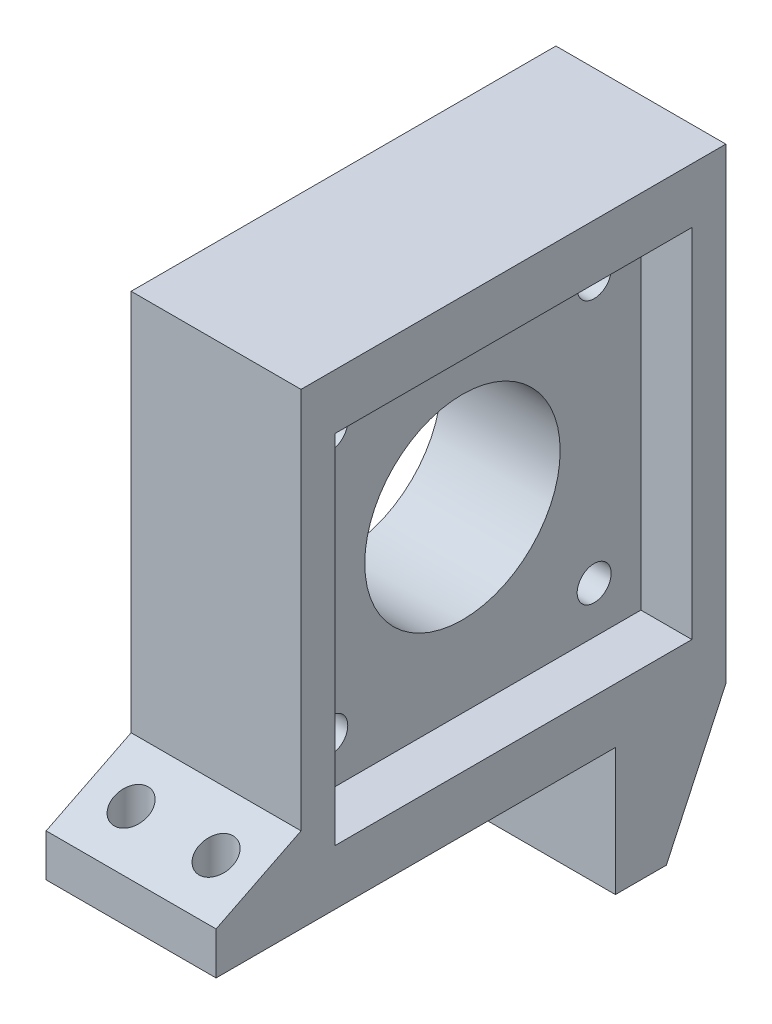
SolidWorks part; units mm, degrees
ref_plane "Front Plane" through (0, 0, 0) normal (0, 0, 1) x (1, 0, 0)
ref_plane "Top Plane" through (0, 0, 0) normal (0, 1, 0) x (1, 0, 0)
ref_plane "Right Plane" through (0, 0, 0) normal (1, 0, 0) x (0, 0, -1)
sketch "Sketch1" plane through (0, 0, 0) normal (0, 1, 0) x (1, 0, 0)
  line L1 (0, 0) -> (-20, 0)
  line L2 (0, 0) -> (0, -50)
  line L3 (0, -50) -> (-20, -50)
  line L4 (-20, 0) -> (-20, -50)
  dimension "D1" = 20
  dimension "D2" = 50
extrude "Boss-Extrude1" add sketch "Sketch1" along normal blind 70
sketch "Sketch2" plane through (0, 0, 0) normal (1, 0, 0) x (0, 0, -1)
  line L0 (-50, 70) -> (0, 70) construction
  line L1 (0, 70) -> (0, 0) construction
  line L2 (0, 42.5) -> (-50, 42.5) construction
  line L3 (-25, 70) -> (-25, 0) construction
  line L4 (-25, 70) -> (-25, 0) construction
  line L7 (-50, 70) -> (-50, 0) construction
  circle A0 centre (-9.5, 58) radius 2
  circle A4 centre (-25, 42.5) radius 11.5
  circle A5 centre (-9.5, 27) radius 2
  circle A8 centre (-40.5, 27) radius 2
  circle A9 centre (-40.5, 58) radius 2
  dimension "D1" = 4
  dimension "D2" = 12
  dimension "D3" = 15.5
  dimension "D6" = 23
  dimension "D7" = 0
  dimension "D8" = 0
  dimension "D4" = 15.5
  dimension "D5" = 0
extrude "Cut-Extrude2" cut sketch "Sketch2" against normal blind 60
sketch "Sketch4" plane through (0, 0, 0) normal (1, 0, 0) x (0, 0, -1)
  line L1 (-50, 0) -> (-13, 0)
  line L2 (-50, 0) -> (-50, 15)
  line L3 (-50, 15) -> (-13, 15)
  line L4 (-13, 0) -> (-13, 15)
  circle A0 centre (-25, 42.5) radius 11.5 construction
  dimension "D1" = 15
  dimension "D2" = 12
extrude "Cut-Extrude3" cut sketch "Sketch4" against normal blind 60
sketch "Sketch8" plane through (0, 0, 0) normal (0, 0, -1) x (-1, 0, 0)
  line L0 (0, 0) -> (20, 0) construction
  line L1 (20, 70) -> (20, 0) construction
  circle A0 centre (15, 6) radius 2
  dimension "D1" = 4
  dimension "D2" = 6
  dimension "D3" = 5
extrude "Cut-Extrude5" cut sketch "Sketch8" against normal blind 15
sketch "Sketch9" plane through (0, 0, 0) normal (1, 0, 0) x (0, 0, -1)
  line L0 (0, 42.5) -> (-50, 42.5) construction
  line L1 (-4, 63.5) -> (-46, 63.5)
  line L2 (-4, 63.5) -> (-4, 21.5)
  line L3 (-4, 21.5) -> (-46, 21.5)
  line L4 (-46, 63.5) -> (-46, 21.5)
  line L5 (0, 70) -> (0, 0) construction
  line L6 (-50, 70) -> (-50, 15) construction
  line L7 (-25, 70) -> (-25, 15) construction
  line L8 (-50, 70) -> (0, 70) construction
  line L9 (-13, 15) -> (-50, 15) construction
  circle A0 centre (-25, 42.5) radius 11.5 construction
  dimension "D1" = 0
  dimension "D2" = 42
  dimension "D3" = 21
  dimension "D4" = 42
  dimension "D5" = 21
  dimension "D6" = 0
extrude "Cut-Extrude6" cut sketch "Sketch9" against normal blind 6
sketch "Sketch10" plane through (0, 0, 0) normal (0, 0, -1) x (-1, 0, 0)
  line L0 (0, 70) -> (0, 0) construction
  circle A0 centre (5, 6) radius 2
  circle A1 centre (15, 6) radius 2 construction
  dimension "D1" = 4
  dimension "D2" = 5
  dimension "D3" = 0
extrude "Cut-Extrude7" cut sketch "Sketch10" against normal blind 7
sketch "Sketch11" plane through (0, 0, 0) normal (1, 0, 0) x (0, 0, -1)
  line L7 (-7, 0) -> (0, 0)
  line L8 (-13, 0) -> (0, 0) construction
  line L9 (0, 0) -> (0, 15)
  line L10 (0, 70) -> (0, 0) construction
  line L11 (0, 15) -> (-7, 0)
  line L12 (-13, 15) -> (-50, 15) construction
  dimension "D1" = 0
  dimension "D2" = 6
extrude "Cut-Extrude8" cut sketch "Sketch11" against normal blind 30
sketch "Sketch12" plane through (0, 0, 50) normal (0, 0, 1) x (1, 0, 0)
  line L0 (-20, 70) -> (-20, 15) construction
  line L1 (0, 15) -> (-20, 15)
  line L2 (0, 15) -> (0, 20)
  line L3 (0, 20) -> (-20, 20)
  line L4 (-20, 15) -> (-20, 20)
  dimension "D1" = 5
extrude "Boss-Extrude2" add sketch "Sketch12" along normal blind 10
sketch "Sketch14" plane through (0, 0, 0) normal (1, 0, 0) x (0, 0, -1)
  line L0 (-50, 20) -> (-60, 20)
  line L1 (-60, 20) -> (-50, 20) construction
  line L2 (-60, 20) -> (-50, 25)
  line L3 (-50, 70) -> (-50, 20) construction
  line L4 (-50, 25) -> (-50, 20)
  dimension "D1" = 5
extrude "Boss-Extrude3" add sketch "Sketch14" against normal up to vertex (20 mm away) up to point (-20, 20, 60)
sketch "Sketch15" plane through (0, 15, 0) normal (0, -1, 0) x (-1, 0, 0)
  line L0 (0, -13) -> (0, -60) construction
  line L1 (20, -13) -> (20, -60) construction
  line L2 (20, -60) -> (0, -60) construction
  circle A0 centre (5, -55) radius 2
  circle A1 centre (15, -55) radius 2
  dimension "D1" = 4
  dimension "D2" = 4
  dimension "D3" = 5
  dimension "D4" = 5
  dimension "D5" = 5
  dimension "D6" = 5
extrude "Cut-Extrude9" cut sketch "Sketch15" against normal blind 10
